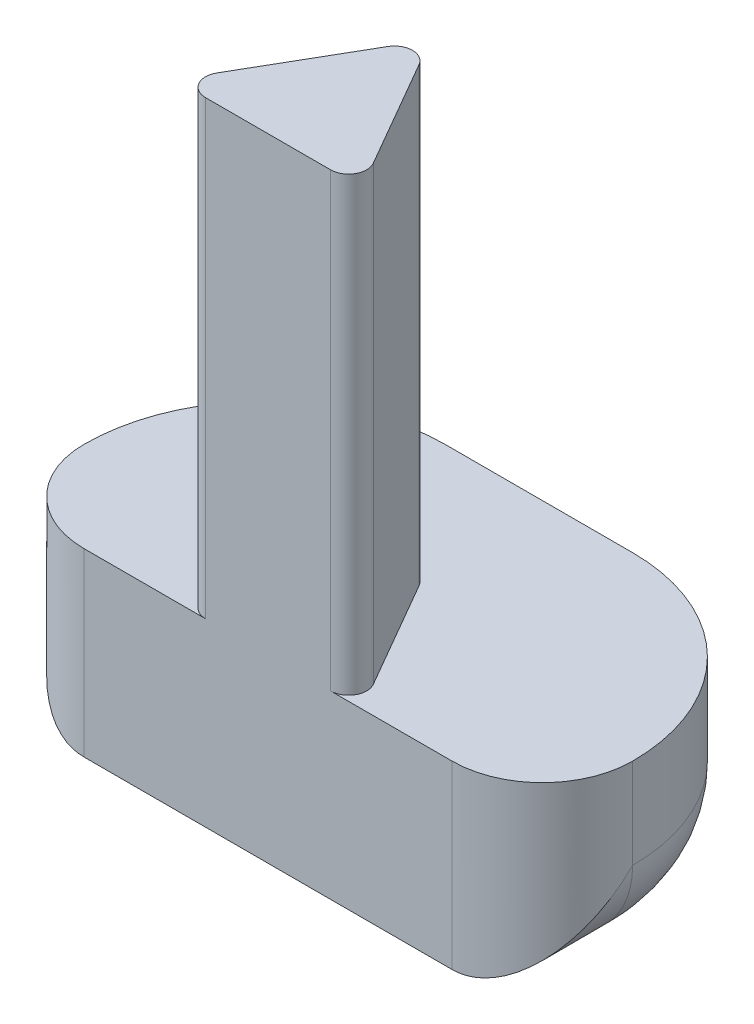
SolidWorks part; units mm, degrees
material "PLA 100% Infill"
ref_plane "Front Plane" through (0, 0, 0) normal (0, 0, 1) x (1, 0, 0)
ref_plane "Top Plane" through (0, 0, 0) normal (0, 1, 0) x (1, 0, 0)
ref_plane "Right Plane" through (0, 0, 0) normal (1, 0, 0) x (0, 0, -1)
sketch "Sketch2" plane through (0, 0, 0) normal (0, 1, 0) x (1, 0, 0)
  line L0 (0, 0) -> (-2.0785, 0)
  line L1 (-2.0785, 0) -> (-1.0392, 1.8)
  line L2 (-1.0392, 1.8) -> (0, 0)
  dimension "D1" = 1.8
extrude "Boss-Extrude1" add sketch "Sketch2" along normal blind 5
sketch "Sketch3" plane through (0, 0, 0) normal (0, -1, 0) x (1, 0, 0)
  line L0 (-2.0785, 0) -> (0, 0) construction
  line L1 (-4.0785, 0) -> (2, 0)
  line L2 (-4.0785, 0) -> (-4.0785, -1)
  line L3 (-2.0785, -3) -> (0, -3)
  line L4 (2, 0) -> (2, -1)
  arc A0 (0, -3) -> (2, -1) centre (0, -1) ccw
  arc A1 (-2.0785, -3) -> (-4.0785, -1) centre (-2.0785, -1) cw
  point P14 (-4.0785, -3)
  dimension "D4" = 2
  dimension "D1" = 3
  dimension "D2" = 2
  dimension "D3" = 2
extrude "Boss-Extrude2" add sketch "Sketch3" along normal blind 2 contours A0 L4 L1 L2 A1 L3
fillet "Fillet1" radius 1 7 edges at (-4.0785, -2, -0.5) (-3.4927, -2, -2.4142) (-1.0392, -2, -3) (2, -2, -0.5) (1.4142, -2, -2.4142) (-4.0785, -1, 0) (2, -1, 0)
fillet "Fillet2" radius 0.2 3 edges at (0, 2.5, 0) (-2.0785, 2.5, 0) (-1.0392, 2.5, -1.8)
